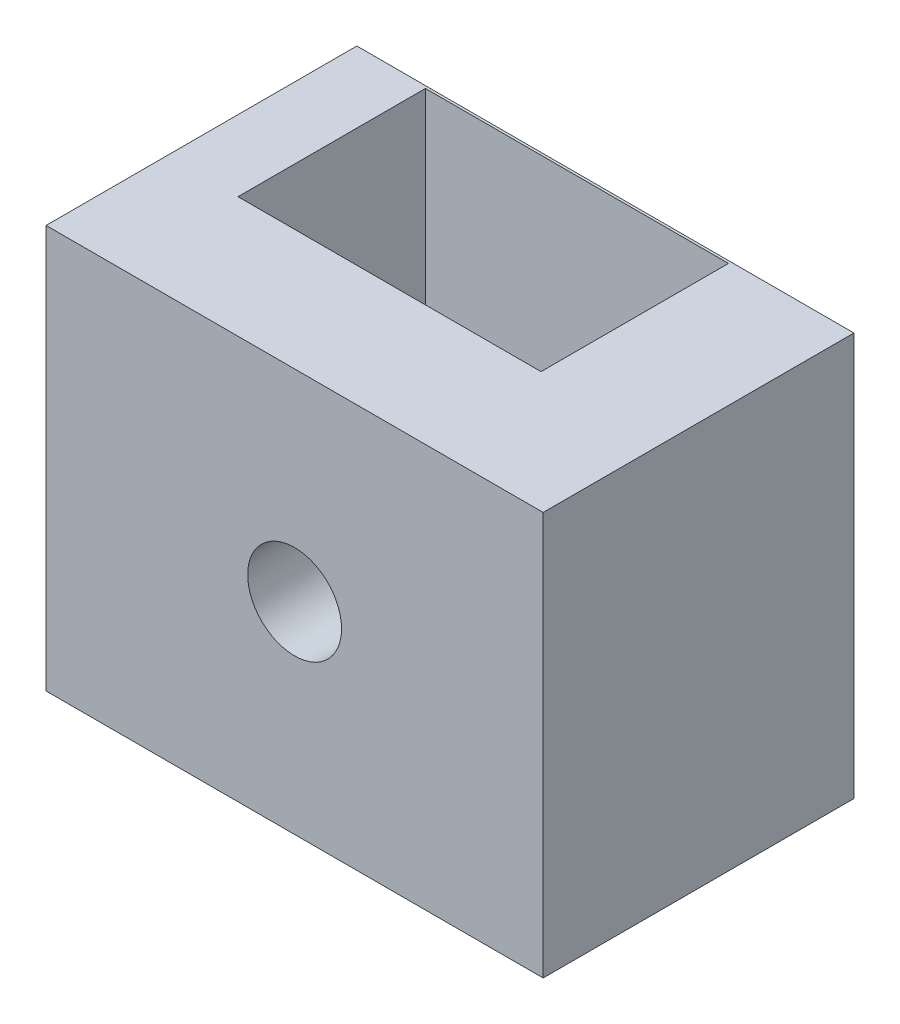
SolidWorks part; units mm, degrees
ref_plane "Front Plane" through (0, 0, 0) normal (0, 0, 1) x (1, 0, 0)
ref_plane "Top Plane" through (0, 0, 0) normal (0, 1, 0) x (1, 0, 0)
ref_plane "Right Plane" through (0, 0, 0) normal (1, 0, 0) x (0, 0, -1)
sketch "Sketch2" plane through (0, 0, 0) normal (0, 0, 1) x (1, 0, 0)
  line L1 (-67.2388, -54.5382) -> (67.2388, -54.5382)
  line L2 (-67.2388, -54.5382) -> (-67.2388, 54.5382)
  line L3 (-67.2388, 54.5382) -> (67.2388, 54.5382)
  line L4 (67.2388, -54.5382) -> (67.2388, 54.5382)
  line L5 (-67.2388, -54.5382) -> (67.2388, 54.5382) construction
  line L6 (-67.2388, 54.5382) -> (67.2388, -54.5382) construction
  point P0 (0, 0)
extrude "Boss-Extrude1" add sketch "Sketch2" along normal blind 84.074
sketch "Sketch3" plane through (0, 0, 84.074) normal (0, 0, 1) x (1, 0, 0)
  circle A0 centre (0, 0) radius 12.7
  dimension "D1" = 25.4
extrude "Cut-Extrude1" cut sketch "Sketch3" against normal blind 127
sketch "Sketch4" plane through (0, 54.5382, 0) normal (0, 1, 0) x (1, 0, 0)
  line L1 (-48.013, -0.6681) -> (33.9651, -0.6681)
  line L2 (-48.013, -0.6681) -> (-48.013, -51.3752)
  line L3 (-48.013, -51.3752) -> (33.9651, -51.3752)
  line L4 (33.9651, -0.6681) -> (33.9651, -51.3752)
extrude "Cut-Extrude2" cut sketch "Sketch4" against normal blind 104.14
